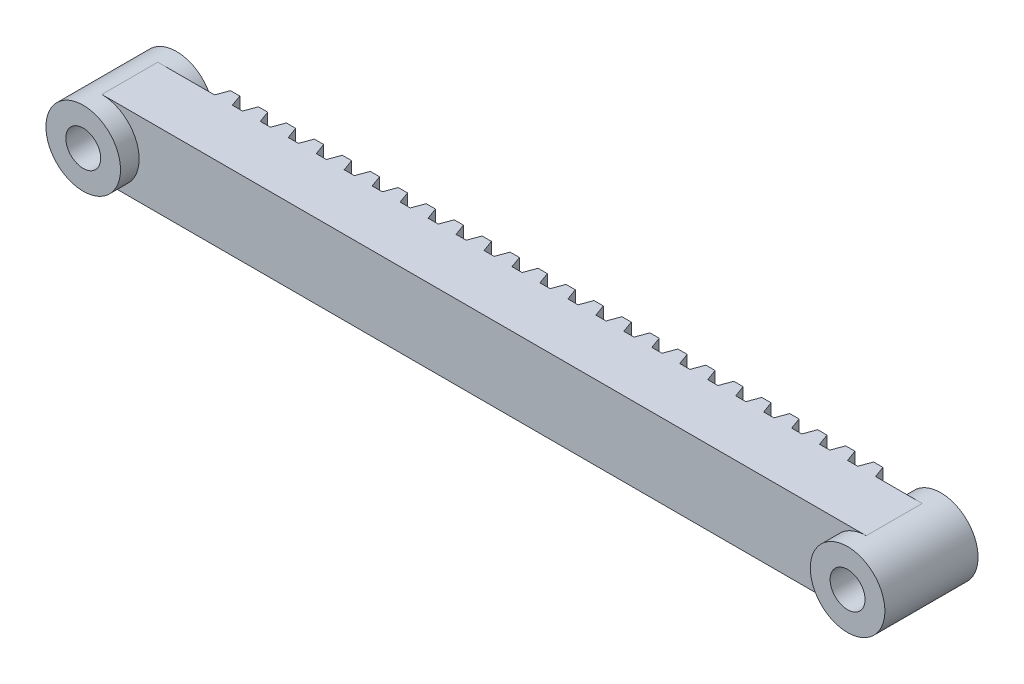
SolidWorks part; units mm, degrees
material "Galvanized Steel"
ref_plane "Front Plane" through (0, 0, 0) normal (0, 0, 1) x (1, 0, 0)
ref_plane "Top Plane" through (0, 0, 0) normal (0, 1, 0) x (1, 0, 0)
ref_plane "Right Plane" through (0, 0, 0) normal (1, 0, 0) x (0, 0, -1)
sketch "Sketch1" plane through (0, 0, 0) normal (0, 0, 1) x (1, 0, 0)
  line L0 (0, 28.5058) -> (0, -31.3137) construction
  circle A0 centre (-82, 0) radius 3.75
  circle A1 centre (-82, 0) radius 8
  circle A2 centre (82, 0) radius 3.75
  circle A3 centre (82, 0) radius 8
  dimension "D1" = 16
  dimension "D2" = 7.5
  dimension "D3" = 82
extrude "Boss-Extrude1" add sketch "Sketch1" along normal blind 10 and the other way blind 10
sketch "Sketch2" plane through (0, 0, 0) normal (1, 0, 0) x (0, 0, -1)
  line L0 (-10, -8) -> (10, -8) construction
  line L1 (-6, 8) -> (6, 8)
  line L2 (-6, 8) -> (-6, -8)
  line L3 (-6, -8) -> (6, -8)
  line L4 (6, 8) -> (6, -8)
  line L5 (-6, 8) -> (6, -8) construction
  line L6 (-6, -8) -> (6, 8) construction
  point P0 (0, 0)
  dimension "D1" = 12
extrude "Boss-Extrude5" add sketch "Sketch2" along normal up to surface and the other way up to surface up to face at (74, 0, -10) other way up to face at (-74, 0, -10)
sketch "Sketch5" plane through (0, 0, 0) normal (0, 1, 0) x (1, 0, 0)
  line L0 (70.0901, 8.5) -> (70.0901, 6)
  line L1 (82, 6) -> (-82, 6) construction
  line L2 (69.0901, 8.5) -> (71.0901, 8.5)
  line L3 (71.0901, 8.5) -> (72, 6)
  line L4 (69.0901, 8.5) -> (68.1801, 6)
  line L5 (68.1801, 6) -> (66, 6)
  line L6 (64.0901, 8.5) -> (64.0901, 6)
  line L7 (63.0901, 8.5) -> (65.0901, 8.5)
  line L8 (65.0901, 8.5) -> (66, 6)
  line L9 (63.0901, 8.5) -> (62.1801, 6)
  line L10 (62.1801, 6) -> (60, 6)
  line L11 (58.0901, 8.5) -> (58.0901, 6)
  line L12 (57.0901, 8.5) -> (59.0901, 8.5)
  line L13 (59.0901, 8.5) -> (60, 6)
  line L14 (57.0901, 8.5) -> (56.1801, 6)
  line L15 (56.1801, 6) -> (54, 6)
  line L16 (52.0901, 8.5) -> (52.0901, 6)
  line L17 (51.0901, 8.5) -> (53.0901, 8.5)
  line L18 (53.0901, 8.5) -> (54, 6)
  line L19 (51.0901, 8.5) -> (50.1801, 6)
  line L20 (50.1801, 6) -> (48, 6)
  line L21 (46.0901, 8.5) -> (46.0901, 6)
  line L22 (45.0901, 8.5) -> (47.0901, 8.5)
  line L23 (47.0901, 8.5) -> (48, 6)
  line L24 (45.0901, 8.5) -> (44.1801, 6)
  line L25 (44.1801, 6) -> (42, 6)
  line L26 (40.0901, 8.5) -> (40.0901, 6)
  line L27 (39.0901, 8.5) -> (41.0901, 8.5)
  line L28 (41.0901, 8.5) -> (42, 6)
  line L29 (39.0901, 8.5) -> (38.1801, 6)
  line L30 (38.1801, 6) -> (36, 6)
  line L31 (34.0901, 8.5) -> (34.0901, 6)
  line L32 (33.0901, 8.5) -> (35.0901, 8.5)
  line L33 (35.0901, 8.5) -> (36, 6)
  line L34 (33.0901, 8.5) -> (32.1801, 6)
  line L35 (32.1801, 6) -> (30, 6)
  line L36 (28.0901, 8.5) -> (28.0901, 6)
  line L37 (27.0901, 8.5) -> (29.0901, 8.5)
  line L38 (29.0901, 8.5) -> (30, 6)
  line L39 (27.0901, 8.5) -> (26.1801, 6)
  line L40 (26.1801, 6) -> (24, 6)
  line L41 (22.0901, 8.5) -> (22.0901, 6)
  line L42 (21.0901, 8.5) -> (23.0901, 8.5)
  line L43 (23.0901, 8.5) -> (24, 6)
  line L44 (21.0901, 8.5) -> (20.1801, 6)
  line L45 (20.1801, 6) -> (18, 6)
  line L46 (16.0901, 8.5) -> (16.0901, 6)
  line L47 (15.0901, 8.5) -> (17.0901, 8.5)
  line L48 (17.0901, 8.5) -> (18, 6)
  line L49 (15.0901, 8.5) -> (14.1801, 6)
  line L50 (14.1801, 6) -> (12, 6)
  line L51 (10.0901, 8.5) -> (10.0901, 6)
  line L52 (9.0901, 8.5) -> (11.0901, 8.5)
  line L53 (11.0901, 8.5) -> (12, 6)
  line L54 (9.0901, 8.5) -> (8.1801, 6)
  line L55 (8.1801, 6) -> (6, 6)
  line L56 (4.0901, 8.5) -> (4.0901, 6)
  line L57 (3.0901, 8.5) -> (5.0901, 8.5)
  line L58 (5.0901, 8.5) -> (6, 6)
  line L59 (3.0901, 8.5) -> (2.1801, 6)
  line L60 (2.1801, 6) -> (0, 6)
  line L61 (-1.9099, 8.5) -> (-1.9099, 6)
  line L62 (-2.9099, 8.5) -> (-0.9099, 8.5)
  line L63 (-0.9099, 8.5) -> (0, 6)
  line L64 (-2.9099, 8.5) -> (-3.8199, 6)
  line L65 (-3.8199, 6) -> (-6, 6)
  line L66 (-7.9099, 8.5) -> (-7.9099, 6)
  line L67 (-8.9099, 8.5) -> (-6.9099, 8.5)
  line L68 (-6.9099, 8.5) -> (-6, 6)
  line L69 (-8.9099, 8.5) -> (-9.8199, 6)
  line L70 (-9.8199, 6) -> (-12, 6)
  line L71 (-13.9099, 8.5) -> (-13.9099, 6)
  line L72 (-14.9099, 8.5) -> (-12.9099, 8.5)
  line L73 (-12.9099, 8.5) -> (-12, 6)
  line L74 (-14.9099, 8.5) -> (-15.8199, 6)
  line L75 (-15.8199, 6) -> (-18, 6)
  line L76 (-19.9099, 8.5) -> (-19.9099, 6)
  line L77 (-20.9099, 8.5) -> (-18.9099, 8.5)
  line L78 (-18.9099, 8.5) -> (-18, 6)
  line L79 (-20.9099, 8.5) -> (-21.8199, 6)
  line L80 (-21.8199, 6) -> (-24, 6)
  line L81 (-25.9099, 8.5) -> (-25.9099, 6)
  line L82 (-26.9099, 8.5) -> (-24.9099, 8.5)
  line L83 (-24.9099, 8.5) -> (-24, 6)
  line L84 (-26.9099, 8.5) -> (-27.8199, 6)
  line L85 (-27.8199, 6) -> (-30, 6)
  line L86 (-31.9099, 8.5) -> (-31.9099, 6)
  line L87 (-32.9099, 8.5) -> (-30.9099, 8.5)
  line L88 (-30.9099, 8.5) -> (-30, 6)
  line L89 (-32.9099, 8.5) -> (-33.8199, 6)
  line L90 (-33.8199, 6) -> (-36, 6)
  line L91 (-37.9099, 8.5) -> (-37.9099, 6)
  line L92 (-38.9099, 8.5) -> (-36.9099, 8.5)
  line L93 (-36.9099, 8.5) -> (-36, 6)
  line L94 (-38.9099, 8.5) -> (-39.8199, 6)
  line L95 (-39.8199, 6) -> (-42, 6)
  line L96 (-43.9099, 8.5) -> (-43.9099, 6)
  line L97 (-44.9099, 8.5) -> (-42.9099, 8.5)
  line L98 (-42.9099, 8.5) -> (-42, 6)
  line L99 (-44.9099, 8.5) -> (-45.8199, 6)
  line L100 (-45.8199, 6) -> (-48, 6)
  line L101 (-49.9099, 8.5) -> (-49.9099, 6)
  line L102 (-50.9099, 8.5) -> (-48.9099, 8.5)
  line L103 (-48.9099, 8.5) -> (-48, 6)
  line L104 (-50.9099, 8.5) -> (-51.8199, 6)
  line L105 (-51.8199, 6) -> (-54, 6)
  line L106 (-55.9099, 8.5) -> (-55.9099, 6)
  line L107 (-56.9099, 8.5) -> (-54.9099, 8.5)
  line L108 (-54.9099, 8.5) -> (-54, 6)
  line L109 (-56.9099, 8.5) -> (-57.8199, 6)
  line L110 (-57.8199, 6) -> (-60, 6)
  line L111 (-61.9099, 8.5) -> (-61.9099, 6)
  line L112 (-62.9099, 8.5) -> (-60.9099, 8.5)
  line L113 (-60.9099, 8.5) -> (-60, 6)
  line L114 (-62.9099, 8.5) -> (-63.8199, 6)
  line L115 (-63.8199, 6) -> (-66, 6)
  line L116 (-67.9099, 8.5) -> (-67.9099, 6)
  line L117 (-68.9099, 8.5) -> (-66.9099, 8.5)
  line L118 (-66.9099, 8.5) -> (-66, 6)
  line L119 (-68.9099, 8.5) -> (-69.8199, 6)
  line L120 (-69.8199, 6) -> (-72, 6)
  line L121 (-72, 6) -> (-72, -6)
  line L122 (82, -6) -> (-82, -6) construction
  line L123 (-72, -6) -> (72, -6)
  line L124 (72, -6) -> (72, 6)
  dimension "D1" = 2.5
  dimension "D2" = 20
  dimension "D3" = 1
  dimension "D4" = 18
  dimension "D5" = 6
  dimension "D6" = 24
extrude "Boss-Extrude6" add sketch "Sketch5" along normal blind 8 and the other way blind 8 contours L123 L124 L3 L2 L4 L5 L8 L7 L9 L10 L13 L12 L14 L15 L18 L17 L19 L20 L23 L22 L24 L25 L28 L27 L29 L30 L33 L32 L34 L35 region at (0.1, 0, -0.6534)
